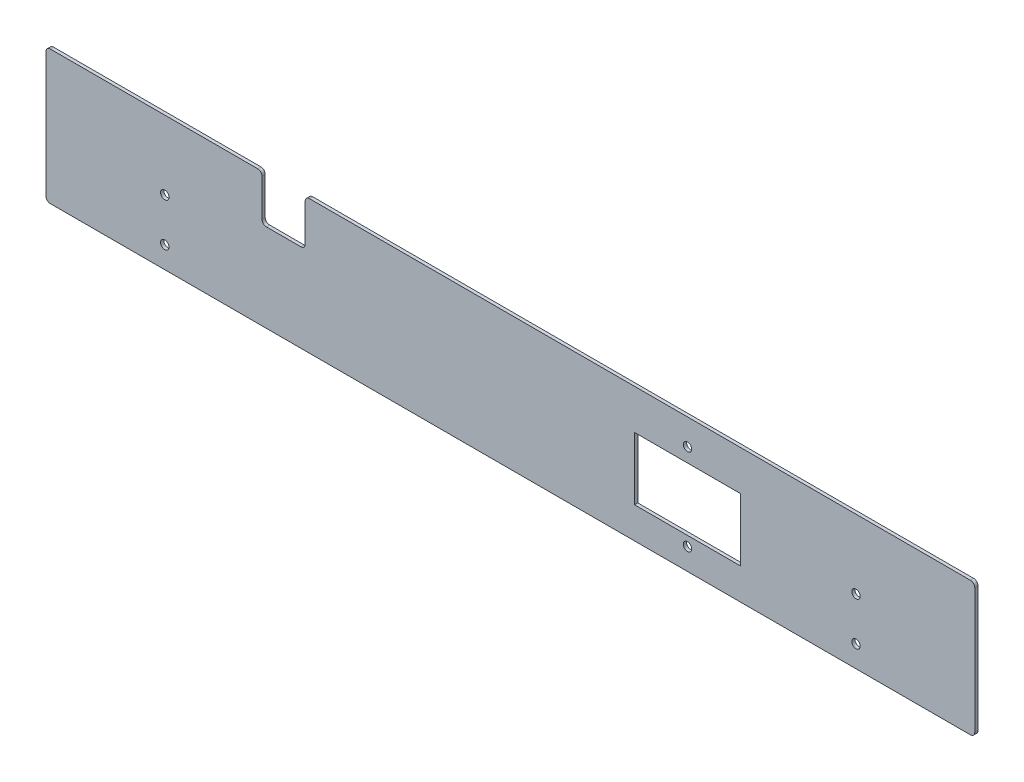
SolidWorks part; units mm, degrees
ref_plane "Front Plane" through (0, 0, 0) normal (0, 0, 1) x (1, 0, 0)
ref_plane "Top Plane" through (0, 0, 0) normal (0, 1, 0) x (1, 0, 0)
ref_plane "Right Plane" through (0, 0, 0) normal (1, 0, 0) x (0, 0, -1)
sketch "Sketch1" plane through (0, 0, 0) normal (0, 0, 1) x (1, 0, 0)
  line L0 (-231.9248, 29.7035) -> (78.0752, 29.7035)
  line L1 (-351.9248, 29.7035) -> (-251.9248, 29.7035)
  line L2 (-351.9248, 29.7035) -> (-351.9248, -32.2965)
  line L3 (-351.9248, -32.2965) -> (78.0752, -32.2965)
  line L4 (78.0752, 29.7035) -> (78.0752, -32.2965)
  line L5 (-79.4248, 11.2035) -> (-30.4248, 11.2035)
  line L6 (-79.4248, 11.2035) -> (-79.4248, -17.7965)
  line L7 (-79.4248, -17.7965) -> (-30.4248, -17.7965)
  line L8 (-30.4248, 11.2035) -> (-30.4248, -17.7965)
  line L10 (-231.9248, 29.7035) -> (-231.9248, 8.4127)
  line L11 (-231.9248, 8.4127) -> (-251.9248, 8.4127)
  line L12 (-251.9248, 29.7035) -> (-251.9248, 8.4127)
  circle A0 centre (-54.9248, 17.7035) radius 1.95
  circle A1 centre (-54.9248, -22.2965) radius 1.95
  point P12 (-54.9248, 11.2035)
  dimension "D3" = 133
  dimension "D4" = 40
  dimension "D1" = 430
  dimension "D2" = 62
  dimension "D5" = 10
  dimension "D6" = 49
  dimension "D7" = 29
  dimension "D8" = 6.5
  dimension "D9" = 20
  dimension "D10" = 100
extrude "Boss-Extrude1" add sketch "Sketch1" along normal blind 1.5
fillet "Fillet1" radius 2 8 edges at (78.0752, -32.2965, 0.75) (-351.9248, -32.2965, 0.75) (-351.9248, 29.7035, 0.75) (-231.9248, 8.4127, 0.75) (-251.9248, 8.4127, 0.75) (-251.9248, 29.7035, 0.75) (-231.9248, 29.7035, 0.75) (78.0752, 29.7035, 0.75)
sketch "Sketch3" plane through (0, 0, 0) normal (0, 0, -1) x (-1, 0, 0)
  line L0 (349.9248, -32.2965) -> (-76.0752, -32.2965) construction
  line L1 (-78.0752, -30.2965) -> (-78.0752, 27.7035) construction
  line L2 (351.9248, 27.7035) -> (351.9248, -30.2965) construction
  circle A0 centre (-23.0752, -22.2965) radius 1.95
  circle A1 centre (-23.0752, -2.2965) radius 1.95
  circle A2 centre (296.9248, -22.2965) radius 1.95
  circle A3 centre (296.9248, -2.2965) radius 1.95
  point P14 (0, 0)
  point P15 (0, 0)
  point P16 (311.7905, -17.1255)
  dimension "D1" = 10
  dimension "D3" = 20
  dimension "D4" = 55
  dimension "D2" = 55
  dimension "D5" = 20
  dimension "D6" = 10
extrude "Cut-Extrude1" cut sketch "Sketch3" against normal blind 10
